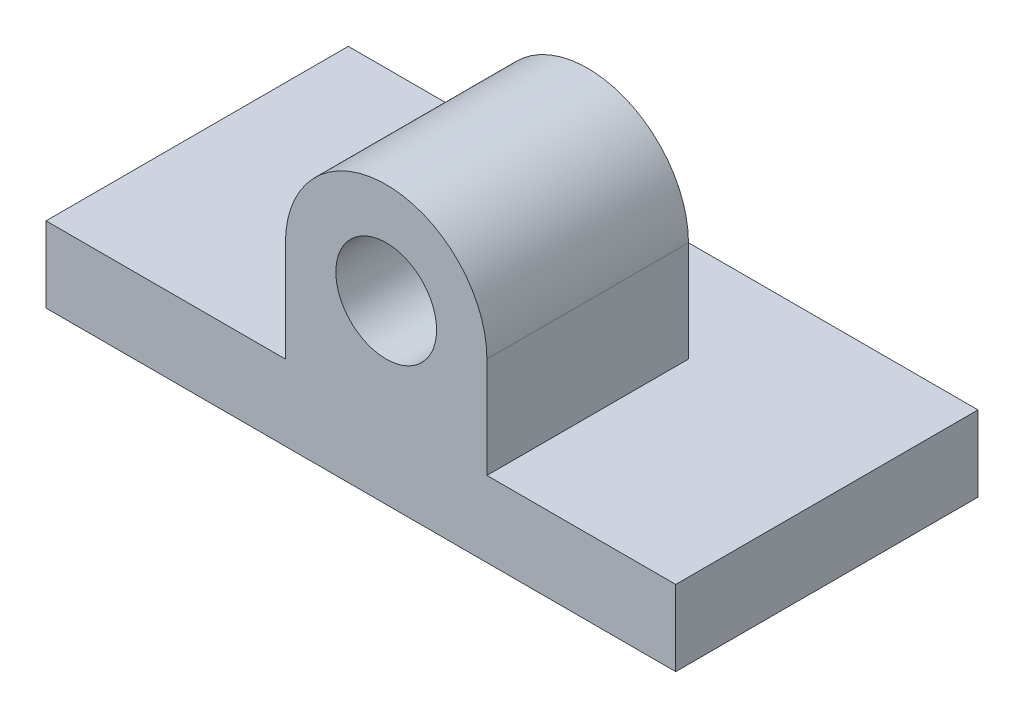
SolidWorks part; units mm, degrees
ref_plane "Front Plane" through (0, 0, 0) normal (0, 0, 1) x (1, 0, 0)
ref_plane "Top Plane" through (0, 0, 0) normal (0, 1, 0) x (1, 0, 0)
ref_plane "Right Plane" through (0, 0, 0) normal (1, 0, 0) x (0, 0, -1)
sketch "Sketch1" plane through (0, 0, 0) normal (0, 0, 1) x (1, 0, 0)
  line L0 (87.5271, 15) -> (87.5271, 35)
  line L1 (0, 0) -> (125, 0)
  line L2 (0, 0) -> (0, 15)
  line L3 (0, 15) -> (125, 15)
  line L4 (125, 0) -> (125, 15)
  line L5 (47.5271, 15) -> (47.5271, 35)
  line L6 (47.5271, 35) -> (87.5271, 35) construction
  arc A0 (87.5271, 35) -> (47.5271, 35) centre (67.5271, 35) ccw
  circle A1 centre (67.5271, 35) radius 10
  dimension "D1" = 125
  dimension "D2" = 15
  dimension "D3" = 40
  dimension "D4" = 20
extrude "Boss-Extrude1" add sketch "Sketch1" against normal blind 60 contours L3 L4 L1 L2
extrude "Boss-Extrude2" add sketch "Sketch1<3>" against normal blind 40 contours A0 L6 A1 | L6 L5 L3 L0 A1 region at (67.5271, 23.5937, 0) region at (82.5271, 35.4472, 0)
sketch "Sketch1<3>" plane through (0, 0, 0) normal (0, 0, 1) x (1, 0, 0) same geometry as "Sketch1"
